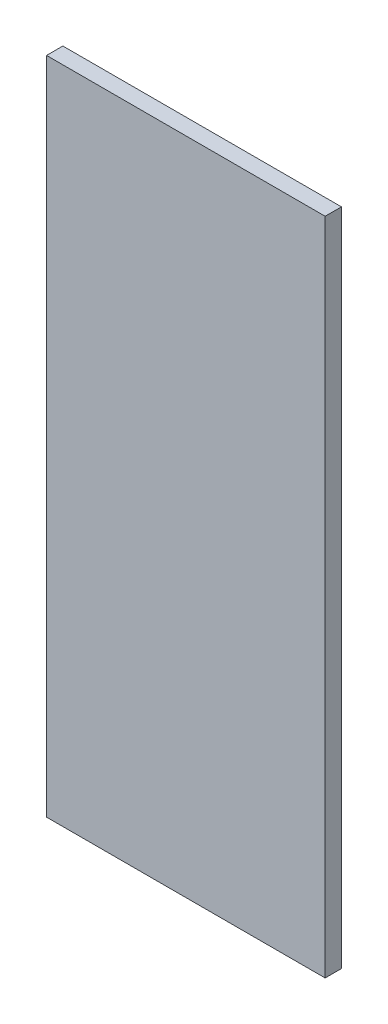
SolidWorks part; units mm, degrees
ref_plane "Front Plane" through (0, 0, 0) normal (0, 0, 1) x (1, 0, 0)
ref_plane "Top Plane" through (0, 0, 0) normal (0, 1, 0) x (1, 0, 0)
ref_plane "Right Plane" through (0, 0, 0) normal (1, 0, 0) x (0, 0, -1)
sketch "Sketch1" plane through (0, 0, 0) normal (0, 0, 1) x (1, 0, 0)
  line L1 (334.3356, 0) -> (160.5887, 0)
  line L2 (334.3356, 0) -> (334.3356, -411.4306)
  line L3 (334.3356, -411.4306) -> (160.5887, -411.4306)
  line L4 (160.5887, 0) -> (160.5887, -411.4306)
  point P4 (160.5887, -411.4306)
extrude "Boss-Extrude1" add sketch "Sketch1" along normal blind 10.16
